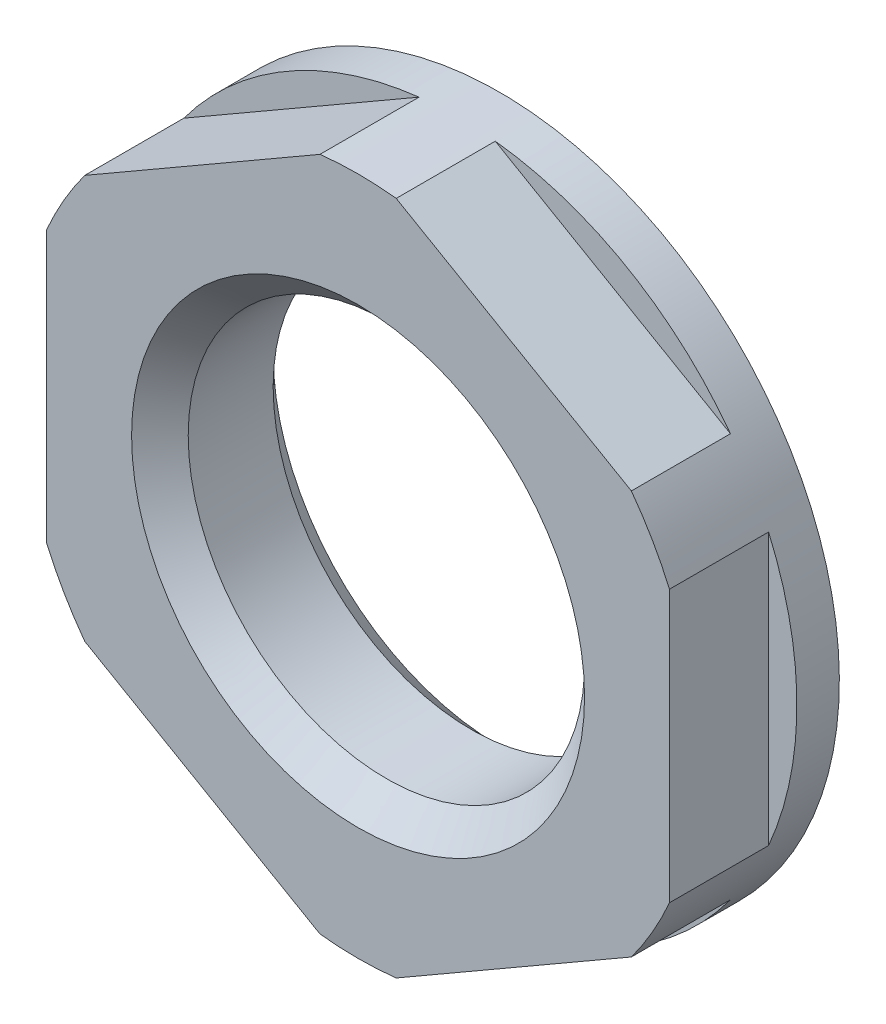
SolidWorks part; units mm, degrees
ref_plane "Спереди" through (0, 0, 0) normal (0, 0, 1) x (1, 0, 0)
ref_plane "Сверху" through (0, 0, 0) normal (0, 1, 0) x (1, 0, 0)
ref_plane "Справа" through (0, 0, 0) normal (1, 0, 0) x (0, 0, -1)
sketch "Эскиз1" plane through (0, 0, 0) normal (0, 0, 1) x (1, 0, 0)
  line L0 (0, 12.7017) -> (0, -12.7017) construction
  line L1 (0, 12.7017) -> (-11, 6.3509)
  line L2 (-11, 6.3509) -> (-11, -6.3509)
  line L3 (-11, -6.3509) -> (0, -12.7017)
  line L4 (0, -12.7017) -> (11, -6.3509)
  line L5 (11, -6.3509) -> (11, 6.3509)
  line L6 (11, 6.3509) -> (0, 12.7017)
  line L7 (11, -6.3509) -> (-11, -6.3509) construction
  dimension "D1" = 120
  dimension "D2" = 22
extrude "Вытянуть1" add sketch "Эскиз1" along normal blind 5
sketch "Эскиз2" plane through (0, 0, 5) normal (0, 0, 1) x (1, 0, 0)
  circle A0 centre (0, 0) radius 12.7017
  circle A1 centre (0, 0) radius 12
  dimension "D1" = 24
extrude "Вырез-Вытянуть1" cut sketch "Эскиз2" against normal through all
sketch "Эскиз4" plane through (0, 0, 0) normal (0, 0, -1) x (-1, 0, 0)
  circle A0 centre (0, 0) radius 12
  circle A1 centre (0, 0) radius 12 construction
extrude "Вытянуть3" add sketch "Эскиз4" against normal blind 1.5
sketch "Эскиз5" plane through (0, 0, 5) normal (0, 0, 1) x (1, 0, 0)
  circle A0 centre (0, 0) radius 7
  dimension "D1" = 14
extrude "Вырез-Вытянуть2" cut sketch "Эскиз5" against normal through all
chamfer "Фаска1" distance 1 angle 45 2 edges at (7, 0, 0) (7, 0, 5)
